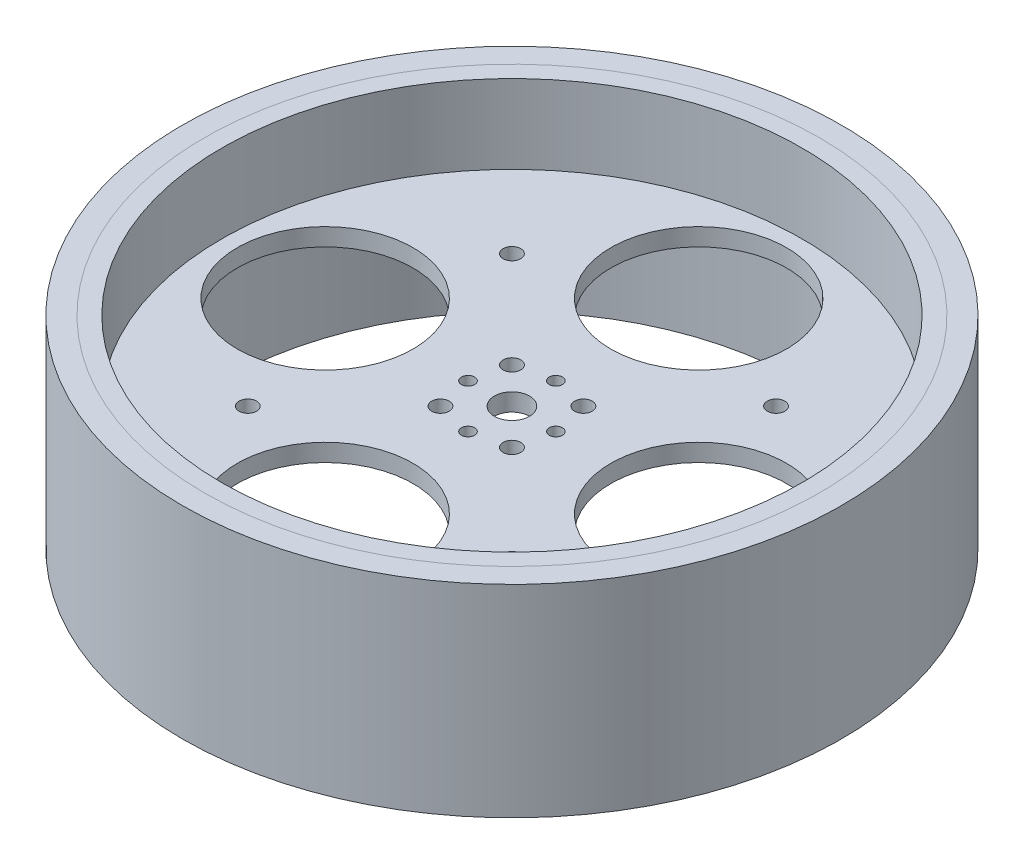
SolidWorks part; units mm, degrees
ref_plane "Front Plane" through (0, 0, 0) normal (0, 0, 1) x (1, 0, 0)
ref_plane "Top Plane" through (0, 0, 0) normal (0, 1, 0) x (1, 0, 0)
ref_plane "Right Plane" through (0, 0, 0) normal (1, 0, 0) x (0, 0, -1)
sketch "Sketch1" plane through (0, 0, 0) normal (0, 1, 0) x (1, 0, 0)
  circle A0 centre (0, 0) radius 4
  circle A4 centre (0, 0) radius 66
  circle A5 centre (0, 0) radius 70
  circle A6 centre (0, 0) radius 75
  circle A7 centre (-10, 0) radius 1.5
  circle A11 centre (-8.1317, -8.1317) radius 2
  circle A12 centre (-8.1317, 8.1317) radius 2
  circle A13 centre (8.1317, 8.1317) radius 2
  circle A14 centre (8.1317, -8.1317) radius 2
  circle A15 centre (0, 10) radius 1.5
  circle A16 centre (10, 0) radius 1.5
  circle A17 centre (0, -10) radius 1.5
  circle A18 centre (-42.5, 0) radius 20
  circle A19 centre (0, 42.5) radius 20
  circle A20 centre (42.5, 0) radius 20
  circle A21 centre (0, -42.5) radius 20
  circle A22 centre (-30.052, -30.052) radius 2
  circle A23 centre (-30.052, 30.052) radius 2
  circle A24 centre (30.052, 30.052) radius 2
  circle A25 centre (30.052, -30.052) radius 2
  point P11 (0, 0)
  point P20 (0, 0)
  point P28 (0, 0)
  point P34 (0, 0)
  point P35 (0, 0)
  point P36 (0, 0)
  point P43 (0, 0)
  point P44 (0, 0)
  dimension "D1" = 8
  dimension "D2" = 4
  dimension "D3" = 10
  dimension "D4" = 42.5
  dimension "D5" = 132
  dimension "D6" = 140
  dimension "D7" = 150
  dimension "D8" = 3
  dimension "D9" = 4
  dimension "D11" = 11.4999
  dimension "D12" = 40
  dimension "D13" = 40
  dimension "D14" = 40
  dimension "D15" = 40
  dimension "D16" = 4
  dimension "D17" = 42.5
  dimension "D18" = 42.5
  dimension "D19" = 42.5
  dimension "D20" = 42.5
  dimension "D25" = 42.5
  dimension "D26" = 42.5
  dimension "D27" = 42.5
  dimension "D28" = 42.5
  dimension "D10" = 4
  dimension "D21" = 4
extrude "Boss-Extrude1" add sketch "Sketch1" along normal blind 2 and the other way blind 2 contours A4 A25 A24 A23 A22 A21 A20 A19 A18 A17 A16 A15 A14 A13 A12 A11 A7 A0 region at (-64.1332, 0, 0)
extrude "Boss-Extrude2" add sketch "Sketch1<3>" along normal blind 19.9 and the other way blind 26.1 contours A5 A4 region at (-68.0201, 0, 0)
sketch "Sketch1<3>" plane through (0, 0, 0) normal (0, 1, 0) x (1, 0, 0) same geometry as "Sketch1"
extrude "Boss-Extrude3" add sketch "Sketch1<4>" along normal blind 19.9 and the other way blind 26.1 separate body contours A6 A5 region at (-72.8787, 0, 0)
sketch "Sketch1<4>" plane through (0, 0, 0) normal (0, 1, 0) x (1, 0, 0) same geometry as "Sketch1"
